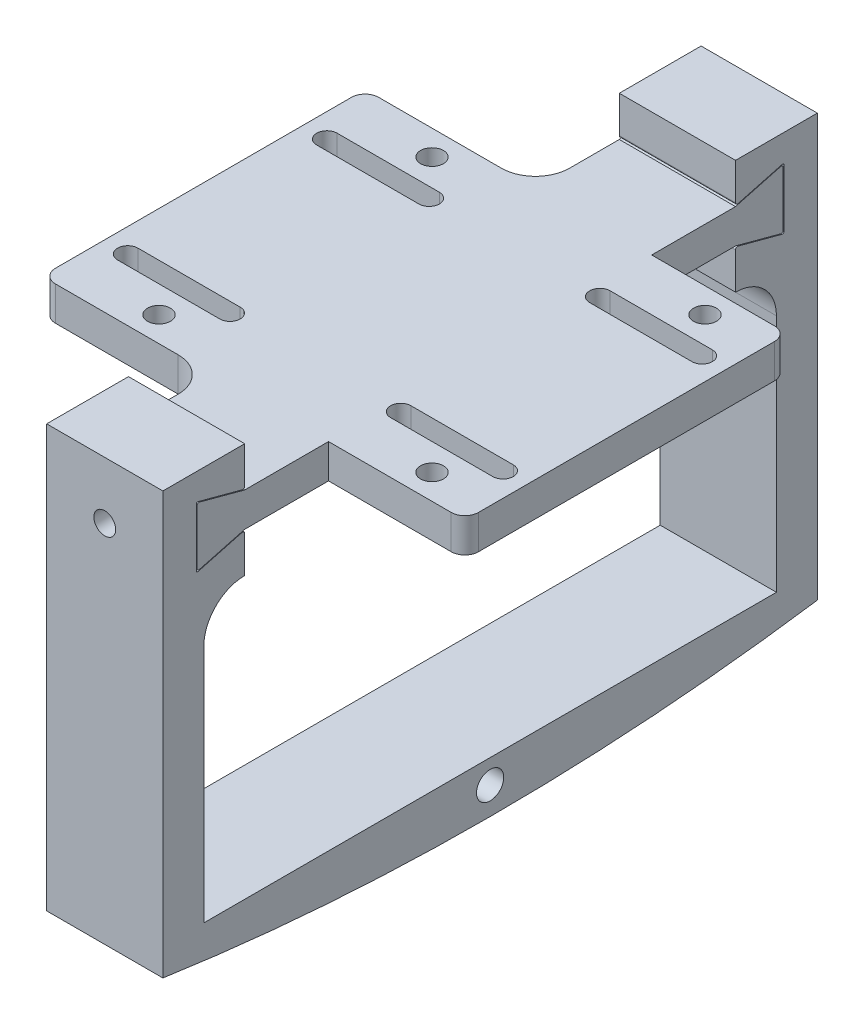
SolidWorks part; units mm, degrees
note: The reader was unsure of these and kept them because the rebuilt part matched: shared geometry of "Sketch6<2>".
ref_plane "Front Plane" through (0, 0, 0) normal (0, 0, 1) x (1, 0, 0)
ref_plane "Top Plane" through (0, 0, 0) normal (0, 1, 0) x (1, 0, 0)
ref_plane "Right Plane" through (0, 0, 0) normal (1, 0, 0) x (0, 0, -1)
sketch "Sketch1" plane through (0, 0, 0) normal (0, 1, 0) x (1, 0, 0)
  line L0 (10.025, 14.605) -> (25.025, 14.605) construction
  line L1 (-20.025, -20.025) -> (20.025, -20.025) construction
  line L2 (-20.025, -20.025) -> (-20.025, 20.025) construction
  line L3 (-20.025, 20.025) -> (20.025, 20.025) construction
  line L4 (20.025, -20.025) -> (20.025, 20.025) construction
  line L5 (-20.025, -20.025) -> (20.025, 20.025) construction
  line L6 (-20.025, 20.025) -> (20.025, -20.025) construction
  line L7 (10.025, 16.105) -> (25.025, 16.105)
  line L8 (10.025, 13.105) -> (25.025, 13.105)
  line L9 (-30.025, 14.605) -> (-15.025, 14.605) construction
  line L10 (-30.025, 16.105) -> (-15.025, 16.105)
  line L11 (-30.025, 13.105) -> (-15.025, 13.105)
  line L12 (-49.445, 0) -> (49.445, 0) construction
  line L13 (-30.025, -14.605) -> (-15.025, -14.605) construction
  line L14 (-30.025, -16.105) -> (-15.025, -16.105)
  line L15 (-30.025, -13.105) -> (-15.025, -13.105)
  line L16 (10.025, -14.605) -> (25.025, -14.605) construction
  line L17 (10.025, -16.105) -> (25.025, -16.105)
  line L18 (10.025, -13.105) -> (25.025, -13.105)
  line L19 (-33.525, 0) -> (28.525, 0) construction
  line L20 (26.525, 23.705) -> (-31.525, 23.705)
  line L21 (28.525, 21.705) -> (28.525, -21.705)
  line L22 (26.525, -23.705) -> (-31.525, -23.705)
  line L23 (-33.525, 21.705) -> (-33.525, -21.705)
  line L24 (-49.239, 36) -> (40.661, -36) construction
  line L25 (-49.239, 36) -> (40.661, 36) construction
  line L26 (-49.239, 36) -> (-49.239, -36) construction
  line L27 (-49.239, -36) -> (40.661, -36) construction
  line L28 (40.661, 36) -> (40.661, -36) construction
  line L29 (-49.239, -36) -> (40.661, 36) construction
  circle A0 centre (-20.025, 20.025) radius 1.68
  circle A1 centre (20.025, -20.025) radius 1.68
  circle A2 centre (20.025, 20.025) radius 1.68
  circle A3 centre (-20.025, -20.025) radius 1.68
  arc A4 (10.025, 16.105) -> (10.025, 13.105) centre (10.025, 14.605) ccw
  arc A5 (25.025, 13.105) -> (25.025, 16.105) centre (25.025, 14.605) ccw
  arc A6 (-30.025, 16.105) -> (-30.025, 13.105) centre (-30.025, 14.605) ccw
  arc A7 (-15.025, 13.105) -> (-15.025, 16.105) centre (-15.025, 14.605) ccw
  arc A8 (-30.025, -16.105) -> (-30.025, -13.105) centre (-30.025, -14.605) cw
  arc A9 (-15.025, -13.105) -> (-15.025, -16.105) centre (-15.025, -14.605) cw
  arc A10 (10.025, -16.105) -> (10.025, -13.105) centre (10.025, -14.605) cw
  arc A11 (25.025, -13.105) -> (25.025, -16.105) centre (25.025, -14.605) cw
  arc A12 (26.525, 23.705) -> (28.525, 21.705) centre (26.525, 21.705) cw
  arc A13 (28.525, -21.705) -> (26.525, -23.705) centre (26.525, -21.705) cw
  arc A14 (-31.525, -23.705) -> (-33.525, -21.705) centre (-31.525, -21.705) cw
  arc A15 (-31.525, 23.705) -> (-33.525, 21.705) centre (-31.525, 21.705) ccw
  point P0 (0, 0)
  point P9 (17.525, 14.605)
  point P15 (0, 0)
  point P21 (-22.525, 14.605)
  point P32 (-22.525, -14.605)
  point P39 (17.525, -14.605)
  point P48 (-31.525, 14.605)
  dimension "D2" = 3.36
  dimension "D4" = 1.5
  dimension "D14" = 2
  dimension "D1" = 40.05
  dimension "D5" = 2.24
  dimension "D6" = 5
  dimension "D7" = 18
  dimension "D8" = 18
  dimension "D9" = 2.24
  dimension "D10" = 5
  dimension "D11" = 2
  dimension "D12" = 2
  dimension "D13" = 2
  dimension "D15" = 72
  dimension "D16" = 89.9
  dimension "D3" = 2
extrude "Boss-Extrude1" add sketch "Sketch1" against normal blind 5
sketch "Sketch3" plane through (0, 0, 0) normal (0, 1, 0) x (1, 0, 0)
  line L0 (26.525, 23.705) -> (-31.525, 23.705) construction
  line L1 (-8.525, 23.705) -> (8.525, 23.705)
  line L2 (-8.525, 23.705) -> (-8.525, 43)
  line L3 (-8.525, 43) -> (8.525, 43)
  line L4 (8.525, 23.705) -> (8.525, 43)
  line L7 (-49.239, 36) -> (40.661, 36) construction
  line L8 (-2.75, 0) -> (2.75, 0) construction
  line L9 (8.525, -23.705) -> (8.525, -43)
  line L10 (-8.525, -43) -> (8.525, -43)
  line L11 (-8.525, -23.705) -> (-8.525, -43)
  line L12 (-8.525, -23.705) -> (8.525, -23.705)
  line L13 (-8.525, 43) -> (8.525, 23.705) construction
  line L14 (8.525, 43) -> (-8.525, 23.705) construction
  line L15 (0, -2.75) -> (0, 2.75) construction
  line L16 (8.525, 14.605) -> (8.525, 23.705) construction
  arc A0 (10.025, 16.105) -> (10.025, 13.105) centre (10.025, 14.605) ccw construction
  point P6 (0, 33.3525)
  dimension "D1" = 7
extrude "Boss-Extrude2" add sketch "Sketch3" against normal up to surface (5 mm away) up to face at (17.525, -5, 14.605)
sketch "Sketch6" plane through (8.525, 0, 0) normal (1, 0, 0) x (0, 0, -1)
  line L0 (43, 1.8756) -> (43, -6.8756)
  line L1 (23.705, -5) -> (23.705, 0) construction
  line L2 (43, -5) -> (43, 0) construction
  line L3 (43, 1.8756) -> (36, 0)
  line L4 (23.705, 0) -> (43, 0) construction
  line L5 (23.705, -5) -> (23.705, 0) construction
  line L6 (43, -2.5) -> (36, -2.5) construction
  line L7 (36, 0) -> (36, -5)
  line L8 (43, -6.8756) -> (36, -5)
  line L9 (0, 2.75) -> (0, -2.75) construction
  line L10 (-43, -2.5) -> (-36, -2.5) construction
  line L11 (-43, -6.8756) -> (-36, -5)
  line L12 (-36, 0) -> (-36, -5)
  line L13 (-43, 1.8756) -> (-36, 0)
  line L14 (-43, 1.8756) -> (-43, -6.8756)
  point P12 (23.705, -2.5)
  dimension "D1" = 75
  dimension "D2" = 7
extrude "Boss-Extrude3" add sketch "Sketch6" against normal up to surface (17.05 mm away) up to face at (-8.525, -2.5, -33.3525)
sketch "Sketch7" plane through (0, 0, 0) normal (1, 0, 0) x (0, 0, -1)
  line L0 (-48, 5.8756) -> (-36, 5.8756)
  line L1 (-36, 5.8756) -> (-36, -10.8756)
  line L2 (23.705, -5) -> (36, -5) construction
  line L3 (-34, -50) -> (34, -50) construction
  line L4 (-34, -50) -> (-34, -6) construction
  line L5 (-34, -6) -> (34, -6) construction
  line L6 (34, -50) -> (34, -6) construction
  line L7 (-34, -50) -> (34, -6) construction
  line L8 (-34, -6) -> (34, -50) construction
  line L9 (0, 4.8132) -> (0, -4.8132) construction
  line L10 (-48, 5.8756) -> (-48, -52)
  line L11 (-43, -6.8756) -> (-43, 1.8756) construction
  line L12 (-36, -10.8756) -> (-42, -10.8756)
  line L13 (-42, -10.8756) -> (-42, -52)
  line L14 (34, -6) -> (-34, -50) construction
  line L15 (-42, -52) -> (42, -52)
  line L16 (-48, -52) -> (-48, -56)
  line L17 (-1.9365, -56) -> (1.9365, -56)
  line L18 (0, -52) -> (0, -56)
  line L19 (34, -50) -> (-34, -6) construction
  line L20 (48, -52) -> (48, -56)
  line L21 (42, -10.8756) -> (42, -52)
  line L22 (36, -10.8756) -> (42, -10.8756)
  line L23 (48, 5.8756) -> (48, -52)
  line L24 (34, -50) -> (34, -6)
  line L25 (36, 5.8756) -> (36, -10.8756)
  line L26 (48, 5.8756) -> (36, 5.8756)
  circle A0 centre (0, -55.5) radius 2
  arc A1 (-48, -56) -> (48, -56) centre (0, 271.3929) ccw
  point P3 (0, -28)
  dimension "D13" = 2
  dimension "D11" = 4
  dimension "D1" = 44
  dimension "D2" = 1
  dimension "D3" = 68
  dimension "D5" = 5
  dimension "D6" = 4
  dimension "D7" = 4
  dimension "D8" = 6
  dimension "D9" = 2
  dimension "D10" = 4
  dimension "D12" = 1.5
fillet "Fillet1" radius 5 2 edges at (-8.525, -2.5, -23.705) (-8.525, -2.5, 23.705)
extrude "Boss-Extrude4" add sketch "Sketch7" along normal up to surface and the other way up to surface separate body
extrude "Cut-Extrude1" cut sketch "Sketch6<2>" against normal through all
sketch "Sketch6<2>" plane through (8.525, 0, 0) normal (1, 0, 0) x (0, 0, -1) same geometry as "Sketch6"
sketch3d "3DSketch1"
  line L0 (8.525, -7.006, 43.1) -> (8.525, -5.1035, 36)
  line L1 (8.525, 2.006, 43.1) -> (8.525, -7.006, 43.1)
  line L2 (8.525, 0.1035, 36) -> (8.525, 2.006, 43.1)
  line L3 (8.525, -7.006, 43.1) -> (8.525, -5.1035, 36)
  line L4 (8.525, 2.006, 43.1) -> (8.525, -7.006, 43.1)
  line L5 (8.525, 0.1035, 36) -> (8.525, 2.006, 43.1)
  line L6 (8.525, 0.1035, -36) -> (8.525, -5.1035, -36)
  line L7 (8.525, 0.1035, -36) -> (8.525, 2.006, -43.1)
  line L8 (8.525, 2.006, -43.1) -> (8.525, -7.006, -43.1)
  line L9 (8.525, -7.006, -43.1) -> (8.525, -5.1035, -36)
  line L12 (8.525, 0.1035, 36) -> (8.525, -5.1035, 36)
  dimension "D1" = 0.1
extrude "Cut-Extrude2" cut sketch "3DSketch1" along direction (1, 0, 0) on the side against the normal through all contours L3 L12 L5 L4 | L9 L6 L7 L8
fillet "Fillet2" radius 0.3 4 edges at (0, 1.8756, -43) (0, -6.8756, -43) (0, -6.8756, 43) (0, 1.8756, 43)
fillet "Fillet3" radius 0.3 4 edges
fillet "Fillet4" radius 0.2 4 edges
fillet "Fillet5" radius 6 2 edges at (0, -10.8756, -42) (0, -10.8756, 42)
sketch "Sketch11" plane through (0, 0, -48) normal (0, 0, -1) x (-1, 0, 0)
  line L0 (0, 4.8132) -> (0, -4.8132) construction
  line L1 (-8.525, -2.5) -> (8.525, -2.5) construction
  line L2 (-8.525, 5.8756) -> (-8.525, -56) construction
  line L3 (8.525, 5.8756) -> (8.525, -56) construction
  line L5 (13.525, 0) -> (13.525, -5) construction
  circle A0 centre (0, -2.5) radius 1.6
  point P12 (13.525, -2.5)
  dimension "D1" = 3.2
extrude "Cut-Extrude3" cut sketch "Sketch11" against normal blind 15 contours A0
mirror "Mirror1" about plane through (0, 0, 0) normal (0, 0, 1) of "Cut-Extrude3"
equation "\"D9@Sketch1\"=\"D5@Sketch1\""
equation "\"D10@Sketch1\"=\"D6@Sketch1\""
equation "\"D7@Sketch7\"=\"D6@Sketch7\""
